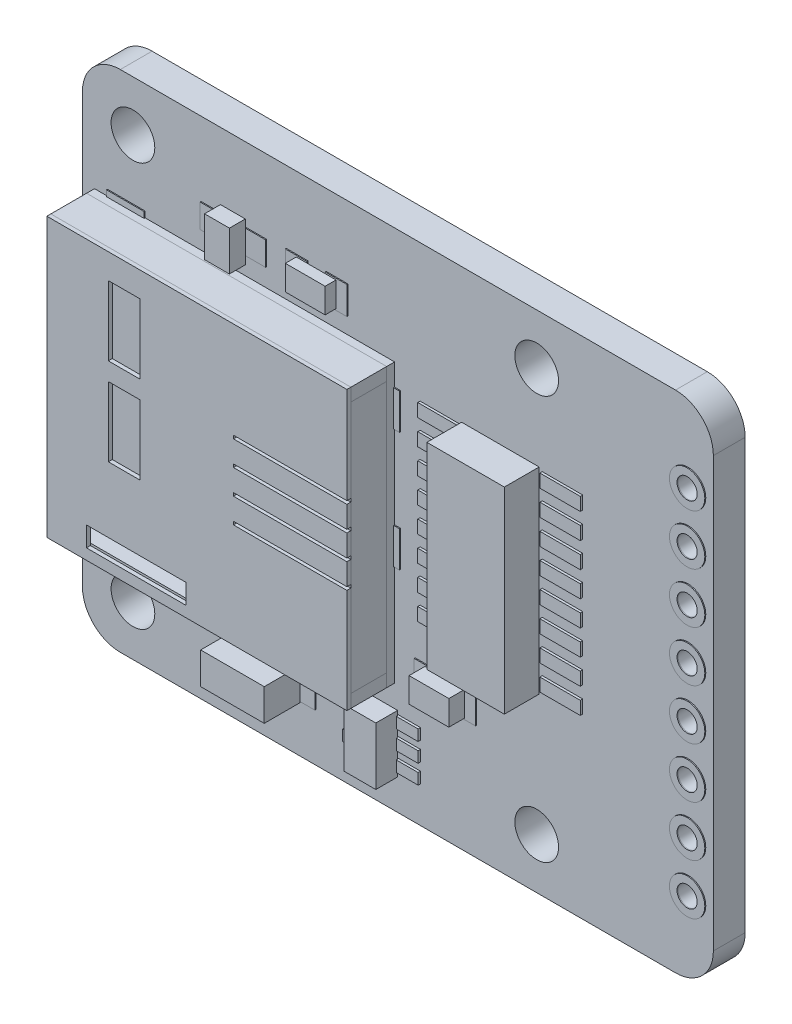
SolidWorks part; units mm, degrees
other "Capot_microSD"
other "PCB_Adafruit_ADA254"
ref_plane "Plan de face" through (0, 0, 0) normal (0, 0, 1) x (1, 0, 0)
ref_plane "Plan de dessus" through (0, 0, 0) normal (0, 1, 0) x (1, 0, 0)
ref_plane "Plan de droite" through (0, 0, 0) normal (1, 0, 0) x (0, 0, -1)
sketch "Esquisse1" plane through (0, 0, 0) normal (0, 0, 1) x (1, 0, 0)
  line L0 (29.845, 0) -> (1.905, 0)
  line L1 (0, 1.905) -> (0, 23.495)
  line L2 (1.905, 25.4) -> (29.845, 25.4)
  line L3 (31.75, 23.495) -> (31.75, 1.905)
  arc A0 (31.75, 1.905) -> (29.845, 0) centre (29.845, 1.905) cw
  arc A1 (1.905, 0) -> (0, 1.905) centre (1.905, 1.905) cw
  arc A2 (0, 23.495) -> (1.905, 25.4) centre (1.905, 23.495) cw
  arc A3 (29.845, 25.4) -> (31.75, 23.495) centre (29.845, 23.495) cw
  circle A4 centre (2.54, 22.86) radius 1.1
  circle A5 centre (2.54, 2.54) radius 1.1
  circle A6 centre (22.86, 22.86) radius 1.1
  circle A7 centre (22.86, 2.54) radius 1.1
  circle A8 centre (30.48, 3.683) radius 0.508
  circle A9 centre (30.48, 6.223) radius 0.508
  circle A10 centre (30.48, 8.763) radius 0.508
  circle A11 centre (30.48, 11.303) radius 0.508
  circle A12 centre (30.48, 13.843) radius 0.508
  circle A13 centre (30.48, 16.383) radius 0.508
  circle A14 centre (30.48, 18.923) radius 0.508
  circle A15 centre (30.48, 21.463) radius 0.508
extrude "PCB_Adafruit_Eagle_31_75x25_4_ep_ESTIMEE1_6" add sketch "Esquisse1" along normal blind 1.6 separate body
sketch "Esquisse2" plane through (0, 0, 0) normal (0, 0, 1) x (1, 0, 0)
  line L1 (0.608, 5.558) -> (15.708, 5.558)
  line L2 (0.608, 5.558) -> (0.608, 19.558)
  line L3 (0.608, 19.558) -> (15.708, 19.558)
  line L4 (15.708, 5.558) -> (15.708, 19.558)
extrude "MicroSD_base_H_ESTIMEE" add sketch "Esquisse2" along normal blind 0.4 from offset 1.6 separate body
sketch "Esquisse3" plane through (0, 0, 0) normal (0, 0, 1) x (1, 0, 0)
  line L1 (0.608, 5.558) -> (15.708, 5.558)
  line L2 (0.608, 5.558) -> (0.608, 6.208)
  line L3 (0.608, 6.208) -> (15.708, 6.208)
  line L4 (15.708, 5.558) -> (15.708, 6.208)
  line L6 (0.608, 18.908) -> (15.708, 18.908)
  line L7 (0.608, 18.908) -> (0.608, 19.558)
  line L8 (0.608, 19.558) -> (15.708, 19.558)
  line L9 (15.708, 18.908) -> (15.708, 19.558)
extrude "MicroSD_flancs" add sketch "Esquisse3" along normal blind 1.8 from offset 2 separate body
sketch "Esquisse4" plane through (0, 0, 0) normal (0, 0, 1) x (1, 0, 0)
  line L1 (15.058, 6.208) -> (15.708, 6.208)
  line L2 (15.058, 6.208) -> (15.058, 18.908)
  line L3 (15.058, 18.908) -> (15.708, 18.908)
  line L4 (15.708, 6.208) -> (15.708, 18.908)
extrude "MicroSD_fond" add sketch "Esquisse4" along normal blind 1.8 from offset 2 separate body
sketch "Esquisse5" plane through (0, 0, 0) normal (0, 0, 1) x (1, 0, 0)
  line L1 (0.608, 5.558) -> (15.708, 5.558)
  line L2 (0.608, 5.558) -> (0.608, 19.558)
  line L3 (0.608, 19.558) -> (15.708, 19.558)
  line L4 (15.708, 5.558) -> (15.708, 19.558)
extrude "MicroSD_capot_metallique" add sketch "Esquisse5" along normal blind 0.2 from offset 3.8 separate body
sketch "Esquisse6" plane through (0, 0, 0) normal (0, 0, 1) x (1, 0, 0)
  line L1 (3.7, 10.4) -> (5.3, 10.4)
  line L2 (3.7, 10.4) -> (3.7, 13.9)
  line L3 (3.7, 13.9) -> (5.3, 13.9)
  line L4 (5.3, 10.4) -> (5.3, 13.9)
  line L6 (3.7, 14.8) -> (5.3, 14.8)
  line L7 (3.7, 14.8) -> (3.7, 18.3)
  line L8 (3.7, 18.3) -> (5.3, 18.3)
  line L9 (5.3, 14.8) -> (5.3, 18.3)
  line L11 (2.6, 6.1) -> (7.6, 6.1)
  line L12 (2.6, 6.1) -> (2.6, 7.1)
  line L13 (2.6, 7.1) -> (7.6, 7.1)
  line L14 (7.6, 6.1) -> (7.6, 7.1)
extrude "Fenetres_capot_simplifiees" cut sketch "Esquisse6" against normal blind 0.2 from offset 4
sketch "Esquisse7" plane through (0, 0, 0) normal (0, 0, 1) x (1, 0, 0)
  line L1 (10, 10.8) -> (15.8, 10.8)
  line L2 (10, 10.8) -> (10, 10.96)
  line L3 (10, 10.96) -> (15.8, 10.96)
  line L4 (15.8, 10.8) -> (15.8, 10.96)
  line L6 (10, 12.05) -> (15.8, 12.05)
  line L7 (10, 12.05) -> (10, 12.21)
  line L8 (10, 12.21) -> (15.8, 12.21)
  line L9 (15.8, 12.05) -> (15.8, 12.21)
  line L11 (10, 13.3) -> (15.8, 13.3)
  line L12 (10, 13.3) -> (10, 13.46)
  line L13 (10, 13.46) -> (15.8, 13.46)
  line L14 (15.8, 13.3) -> (15.8, 13.46)
  line L16 (10, 14.55) -> (15.8, 14.55)
  line L17 (10, 14.55) -> (10, 14.71)
  line L18 (10, 14.71) -> (15.8, 14.71)
  line L19 (15.8, 14.55) -> (15.8, 14.71)
extrude "Fentes_capot_simplifiees" cut sketch "Esquisse7" against normal blind 0.2 from offset 4
sketch "Esquisse8" plane through (0, 0, 0) normal (0, 0, 1) x (1, 0, 0)
  line L1 (4.5, 10.208) -> (9.5, 10.208)
  line L2 (4.5, 10.208) -> (4.5, 10.558)
  line L3 (4.5, 10.558) -> (9.5, 10.558)
  line L4 (9.5, 10.208) -> (9.5, 10.558)
  line L6 (4.5, 11.308) -> (9.5, 11.308)
  line L7 (4.5, 11.308) -> (4.5, 11.658)
  line L8 (4.5, 11.658) -> (9.5, 11.658)
  line L9 (9.5, 11.308) -> (9.5, 11.658)
  line L11 (4.5, 12.408) -> (9.5, 12.408)
  line L12 (4.5, 12.408) -> (4.5, 12.758)
  line L13 (4.5, 12.758) -> (9.5, 12.758)
  line L14 (9.5, 12.408) -> (9.5, 12.758)
  line L16 (4.5, 13.508) -> (9.5, 13.508)
  line L17 (4.5, 13.508) -> (4.5, 13.858)
  line L18 (4.5, 13.858) -> (9.5, 13.858)
  line L19 (9.5, 13.508) -> (9.5, 13.858)
  line L21 (4.5, 14.608) -> (9.5, 14.608)
  line L22 (4.5, 14.608) -> (4.5, 14.958)
  line L23 (4.5, 14.958) -> (9.5, 14.958)
  line L24 (9.5, 14.608) -> (9.5, 14.958)
  line L26 (4.5, 15.708) -> (9.5, 15.708)
  line L27 (4.5, 15.708) -> (4.5, 16.058)
  line L28 (4.5, 16.058) -> (9.5, 16.058)
  line L29 (9.5, 15.708) -> (9.5, 16.058)
  line L31 (4.5, 16.808) -> (9.5, 16.808)
  line L32 (4.5, 16.808) -> (4.5, 17.158)
  line L33 (4.5, 17.158) -> (9.5, 17.158)
  line L34 (9.5, 16.808) -> (9.5, 17.158)
  line L36 (4.5, 17.908) -> (9.5, 17.908)
  line L37 (4.5, 17.908) -> (4.5, 18.258)
  line L38 (4.5, 18.258) -> (9.5, 18.258)
  line L39 (9.5, 17.908) -> (9.5, 18.258)
extrude "Contacts_microSD_simplifies" add sketch "Esquisse8" along normal blind 0.12 from offset 2 separate body
sketch "Esquisse9" plane through (0, 0, 0) normal (0, 0, 1) x (1, 0, 0)
  line L1 (19.132, 8.766) -> (23.032, 8.766)
  line L2 (19.132, 8.766) -> (19.132, 18.666)
  line L3 (19.132, 18.666) -> (23.032, 18.666)
  line L4 (23.032, 8.766) -> (23.032, 18.666)
extrude "IC1_position_Eagle" add sketch "Esquisse9" along normal blind 1.75 from offset 1.65 separate body
sketch "Esquisse10" plane through (0, 0, 0) normal (0, 0, 1) x (1, 0, 0)
  line L1 (14.313, 1.598) -> (15.913, 1.598)
  line L2 (14.313, 1.598) -> (14.313, 4.498)
  line L3 (14.313, 4.498) -> (15.913, 4.498)
  line L4 (15.913, 1.598) -> (15.913, 4.498)
extrude "IC2_position_Eagle" add sketch "Esquisse10" along normal blind 1.1 from offset 1.65 separate body
sketch "Esquisse11" plane through (0, 0, 0) normal (0, 0, 1) x (1, 0, 0)
  line L1 (7.798, 2.375) -> (10.998, 2.375)
  line L2 (7.798, 2.375) -> (7.798, 3.975)
  line L3 (7.798, 3.975) -> (10.998, 3.975)
  line L4 (10.998, 2.375) -> (10.998, 3.975)
extrude "C1_position_Eagle" add sketch "Esquisse11" along normal blind 1.8 from offset 1.65 separate body
sketch "Esquisse12" plane through (0, 0, 0) normal (0, 0, 1) x (1, 0, 0)
  line L1 (17.288, 5.852) -> (19.288, 5.852)
  line L2 (17.288, 5.852) -> (17.288, 7.102)
  line L3 (17.288, 7.102) -> (19.288, 7.102)
  line L4 (19.288, 5.852) -> (19.288, 7.102)
extrude "C2_position_Eagle" add sketch "Esquisse12" along normal blind 0.8 from offset 1.65 separate body
sketch "Esquisse13" plane through (0, 0, 0) normal (0, 0, 1) x (1, 0, 0)
  line L1 (6.995, 20.082) -> (8.245, 20.082)
  line L2 (6.995, 20.082) -> (6.995, 22.082)
  line L3 (6.995, 22.082) -> (8.245, 22.082)
  line L4 (8.245, 20.082) -> (8.245, 22.082)
extrude "ACT_position_Eagle" add sketch "Esquisse13" along normal blind 0.8 from offset 1.65 separate body
sketch "Esquisse14" plane through (0, 0, 0) normal (0, 0, 1) x (1, 0, 0)
  line L1 (10.811, 20.457) -> (12.811, 20.457)
  line L2 (10.811, 20.457) -> (10.811, 21.707)
  line L3 (10.811, 21.707) -> (12.811, 21.707)
  line L4 (12.811, 20.457) -> (12.811, 21.707)
extrude "R1_position_Eagle" add sketch "Esquisse14" along normal blind 0.55 from offset 1.65 separate body
sketch "Esquisse15" plane through (0, 0, 0) normal (0, 0, 1) x (1, 0, 0)
  line L1 (16.9926, 17.8308) -> (19.0246, 17.8308)
  line L2 (16.9926, 17.8308) -> (16.9926, 18.4912)
  line L3 (16.9926, 18.4912) -> (19.0246, 18.4912)
  line L4 (19.0246, 17.8308) -> (19.0246, 18.4912)
extrude "Pad_IC1_0" add sketch "Esquisse15" along normal blind 0.12 from offset 1.6 separate body
sketch "Esquisse16" plane through (0, 0, 0) normal (0, 0, 1) x (1, 0, 0)
  line L1 (23.1394, 17.8308) -> (25.1714, 17.8308)
  line L2 (23.1394, 17.8308) -> (23.1394, 18.4912)
  line L3 (23.1394, 18.4912) -> (25.1714, 18.4912)
  line L4 (25.1714, 17.8308) -> (25.1714, 18.4912)
extrude "Pad_IC1_1" add sketch "Esquisse16" along normal blind 0.12 from offset 1.6 separate body
sketch "Esquisse17" plane through (0, 0, 0) normal (0, 0, 1) x (1, 0, 0)
  line L1 (16.9926, 16.5608) -> (19.0246, 16.5608)
  line L2 (16.9926, 16.5608) -> (16.9926, 17.2212)
  line L3 (16.9926, 17.2212) -> (19.0246, 17.2212)
  line L4 (19.0246, 16.5608) -> (19.0246, 17.2212)
extrude "Pad_IC1_2" add sketch "Esquisse17" along normal blind 0.12 from offset 1.6 separate body
sketch "Esquisse18" plane through (0, 0, 0) normal (0, 0, 1) x (1, 0, 0)
  line L1 (16.9926, 15.2908) -> (19.0246, 15.2908)
  line L2 (16.9926, 15.2908) -> (16.9926, 15.9512)
  line L3 (16.9926, 15.9512) -> (19.0246, 15.9512)
  line L4 (19.0246, 15.2908) -> (19.0246, 15.9512)
extrude "Pad_IC1_3" add sketch "Esquisse18" along normal blind 0.12 from offset 1.6 separate body
sketch "Esquisse19" plane through (0, 0, 0) normal (0, 0, 1) x (1, 0, 0)
  line L1 (23.1394, 16.5608) -> (25.1714, 16.5608)
  line L2 (23.1394, 16.5608) -> (23.1394, 17.2212)
  line L3 (23.1394, 17.2212) -> (25.1714, 17.2212)
  line L4 (25.1714, 16.5608) -> (25.1714, 17.2212)
extrude "Pad_IC1_4" add sketch "Esquisse19" along normal blind 0.12 from offset 1.6 separate body
sketch "Esquisse20" plane through (0, 0, 0) normal (0, 0, 1) x (1, 0, 0)
  line L1 (23.1394, 15.2908) -> (25.1714, 15.2908)
  line L2 (23.1394, 15.2908) -> (23.1394, 15.9512)
  line L3 (23.1394, 15.9512) -> (25.1714, 15.9512)
  line L4 (25.1714, 15.2908) -> (25.1714, 15.9512)
extrude "Pad_IC1_5" add sketch "Esquisse20" along normal blind 0.12 from offset 1.6 separate body
sketch "Esquisse21" plane through (0, 0, 0) normal (0, 0, 1) x (1, 0, 0)
  line L1 (16.9926, 14.0208) -> (19.0246, 14.0208)
  line L2 (16.9926, 14.0208) -> (16.9926, 14.6812)
  line L3 (16.9926, 14.6812) -> (19.0246, 14.6812)
  line L4 (19.0246, 14.0208) -> (19.0246, 14.6812)
extrude "Pad_IC1_6" add sketch "Esquisse21" along normal blind 0.12 from offset 1.6 separate body
sketch "Esquisse22" plane through (0, 0, 0) normal (0, 0, 1) x (1, 0, 0)
  line L1 (23.1394, 14.0208) -> (25.1714, 14.0208)
  line L2 (23.1394, 14.0208) -> (23.1394, 14.6812)
  line L3 (23.1394, 14.6812) -> (25.1714, 14.6812)
  line L4 (25.1714, 14.0208) -> (25.1714, 14.6812)
extrude "Pad_IC1_7" add sketch "Esquisse22" along normal blind 0.12 from offset 1.6 separate body
sketch "Esquisse23" plane through (0, 0, 0) normal (0, 0, 1) x (1, 0, 0)
  line L1 (16.9926, 12.7508) -> (19.0246, 12.7508)
  line L2 (16.9926, 12.7508) -> (16.9926, 13.4112)
  line L3 (16.9926, 13.4112) -> (19.0246, 13.4112)
  line L4 (19.0246, 12.7508) -> (19.0246, 13.4112)
extrude "Pad_IC1_8" add sketch "Esquisse23" along normal blind 0.12 from offset 1.6 separate body
sketch "Esquisse24" plane through (0, 0, 0) normal (0, 0, 1) x (1, 0, 0)
  line L1 (23.1394, 12.7508) -> (25.1714, 12.7508)
  line L2 (23.1394, 12.7508) -> (23.1394, 13.4112)
  line L3 (23.1394, 13.4112) -> (25.1714, 13.4112)
  line L4 (25.1714, 12.7508) -> (25.1714, 13.4112)
extrude "Pad_IC1_9" add sketch "Esquisse24" along normal blind 0.12 from offset 1.6 separate body
sketch "Esquisse25" plane through (0, 0, 0) normal (0, 0, 1) x (1, 0, 0)
  line L1 (16.9926, 11.4808) -> (19.0246, 11.4808)
  line L2 (16.9926, 11.4808) -> (16.9926, 12.1412)
  line L3 (16.9926, 12.1412) -> (19.0246, 12.1412)
  line L4 (19.0246, 11.4808) -> (19.0246, 12.1412)
extrude "Pad_IC1_10" add sketch "Esquisse25" along normal blind 0.12 from offset 1.6 separate body
sketch "Esquisse26" plane through (0, 0, 0) normal (0, 0, 1) x (1, 0, 0)
  line L1 (16.9926, 10.2108) -> (19.0246, 10.2108)
  line L2 (16.9926, 10.2108) -> (16.9926, 10.8712)
  line L3 (16.9926, 10.8712) -> (19.0246, 10.8712)
  line L4 (19.0246, 10.2108) -> (19.0246, 10.8712)
extrude "Pad_IC1_11" add sketch "Esquisse26" along normal blind 0.12 from offset 1.6 separate body
sketch "Esquisse27" plane through (0, 0, 0) normal (0, 0, 1) x (1, 0, 0)
  line L1 (23.1394, 11.4808) -> (25.1714, 11.4808)
  line L2 (23.1394, 11.4808) -> (23.1394, 12.1412)
  line L3 (23.1394, 12.1412) -> (25.1714, 12.1412)
  line L4 (25.1714, 11.4808) -> (25.1714, 12.1412)
extrude "Pad_IC1_12" add sketch "Esquisse27" along normal blind 0.12 from offset 1.6 separate body
sketch "Esquisse28" plane through (0, 0, 0) normal (0, 0, 1) x (1, 0, 0)
  line L1 (23.1394, 10.2108) -> (25.1714, 10.2108)
  line L2 (23.1394, 10.2108) -> (23.1394, 10.8712)
  line L3 (23.1394, 10.8712) -> (25.1714, 10.8712)
  line L4 (25.1714, 10.2108) -> (25.1714, 10.8712)
extrude "Pad_IC1_13" add sketch "Esquisse28" along normal blind 0.12 from offset 1.6 separate body
sketch "Esquisse29" plane through (0, 0, 0) normal (0, 0, 1) x (1, 0, 0)
  line L1 (16.9926, 8.9408) -> (19.0246, 8.9408)
  line L2 (16.9926, 8.9408) -> (16.9926, 9.6012)
  line L3 (16.9926, 9.6012) -> (19.0246, 9.6012)
  line L4 (19.0246, 8.9408) -> (19.0246, 9.6012)
extrude "Pad_IC1_14" add sketch "Esquisse29" along normal blind 0.12 from offset 1.6 separate body
sketch "Esquisse30" plane through (0, 0, 0) normal (0, 0, 1) x (1, 0, 0)
  line L1 (23.1394, 8.9408) -> (25.1714, 8.9408)
  line L2 (23.1394, 8.9408) -> (23.1394, 9.6012)
  line L3 (23.1394, 9.6012) -> (25.1714, 9.6012)
  line L4 (25.1714, 8.9408) -> (25.1714, 9.6012)
extrude "Pad_IC1_15" add sketch "Esquisse30" along normal blind 0.12 from offset 1.6 separate body
sketch "Esquisse31" plane through (0, 0, 0) normal (0, 0, 1) x (1, 0, 0)
  line L1 (1.258, 18.458) -> (3.158, 18.458)
  line L2 (1.258, 18.458) -> (1.258, 19.858)
  line L3 (1.258, 19.858) -> (3.158, 19.858)
  line L4 (3.158, 18.458) -> (3.158, 19.858)
extrude "Pad_X1_0" add sketch "Esquisse31" along normal blind 0.05 from offset 1.6 separate body
sketch "Esquisse32" plane through (0, 0, 0) normal (0, 0, 1) x (1, 0, 0)
  line L1 (0.358, 5.258) -> (2.258, 5.258)
  line L2 (0.358, 5.258) -> (0.358, 6.658)
  line L3 (0.358, 6.658) -> (2.258, 6.658)
  line L4 (2.258, 5.258) -> (2.258, 6.658)
extrude "Pad_X1_1" add sketch "Esquisse32" along normal blind 0.05 from offset 1.6 separate body
sketch "Esquisse33" plane through (0, 0, 0) normal (0, 0, 1) x (1, 0, 0)
  line L1 (14.608, 16.658) -> (16.008, 16.658)
  line L2 (14.608, 16.658) -> (14.608, 18.458)
  line L3 (14.608, 18.458) -> (16.008, 18.458)
  line L4 (16.008, 16.658) -> (16.008, 18.458)
extrude "Pad_X1_2" add sketch "Esquisse33" along normal blind 0.05 from offset 1.6 separate body
sketch "Esquisse34" plane through (0, 0, 0) normal (0, 0, 1) x (1, 0, 0)
  line L1 (14.608, 10.658) -> (16.008, 10.658)
  line L2 (14.608, 10.658) -> (14.608, 12.458)
  line L3 (14.608, 12.458) -> (16.008, 12.458)
  line L4 (16.008, 10.658) -> (16.008, 12.458)
extrude "Pad_X1_3" add sketch "Esquisse34" along normal blind 0.05 from offset 1.6 separate body
sketch "Esquisse35" plane through (0, 0, 0) normal (0, 0, 1) x (1, 0, 0)
  line L1 (4.358, 17.908) -> (5.858, 17.908)
  line L2 (4.358, 17.908) -> (4.358, 18.608)
  line L3 (4.358, 18.608) -> (5.858, 18.608)
  line L4 (5.858, 17.908) -> (5.858, 18.608)
extrude "Pad_X1_4" add sketch "Esquisse35" along normal blind 0.05 from offset 1.6 separate body
sketch "Esquisse36" plane through (0, 0, 0) normal (0, 0, 1) x (1, 0, 0)
  line L1 (4.358, 16.808) -> (5.858, 16.808)
  line L2 (4.358, 16.808) -> (4.358, 17.508)
  line L3 (4.358, 17.508) -> (5.858, 17.508)
  line L4 (5.858, 16.808) -> (5.858, 17.508)
extrude "Pad_X1_5" add sketch "Esquisse36" along normal blind 0.05 from offset 1.6 separate body
sketch "Esquisse37" plane through (0, 0, 0) normal (0, 0, 1) x (1, 0, 0)
  line L1 (3.958, 15.708) -> (5.458, 15.708)
  line L2 (3.958, 15.708) -> (3.958, 16.408)
  line L3 (3.958, 16.408) -> (5.458, 16.408)
  line L4 (5.458, 15.708) -> (5.458, 16.408)
extrude "Pad_X1_6" add sketch "Esquisse37" along normal blind 0.05 from offset 1.6 separate body
sketch "Esquisse38" plane through (0, 0, 0) normal (0, 0, 1) x (1, 0, 0)
  line L1 (4.358, 14.608) -> (5.858, 14.608)
  line L2 (4.358, 14.608) -> (4.358, 15.308)
  line L3 (4.358, 15.308) -> (5.858, 15.308)
  line L4 (5.858, 14.608) -> (5.858, 15.308)
extrude "Pad_X1_7" add sketch "Esquisse38" along normal blind 0.05 from offset 1.6 separate body
sketch "Esquisse39" plane through (0, 0, 0) normal (0, 0, 1) x (1, 0, 0)
  line L1 (3.958, 13.508) -> (5.458, 13.508)
  line L2 (3.958, 13.508) -> (3.958, 14.208)
  line L3 (3.958, 14.208) -> (5.458, 14.208)
  line L4 (5.458, 13.508) -> (5.458, 14.208)
extrude "Pad_X1_8" add sketch "Esquisse39" along normal blind 0.05 from offset 1.6 separate body
sketch "Esquisse40" plane through (0, 0, 0) normal (0, 0, 1) x (1, 0, 0)
  line L1 (4.358, 12.408) -> (5.858, 12.408)
  line L2 (4.358, 12.408) -> (4.358, 13.108)
  line L3 (4.358, 13.108) -> (5.858, 13.108)
  line L4 (5.858, 12.408) -> (5.858, 13.108)
extrude "Pad_X1_9" add sketch "Esquisse40" along normal blind 0.05 from offset 1.6 separate body
sketch "Esquisse41" plane through (0, 0, 0) normal (0, 0, 1) x (1, 0, 0)
  line L1 (4.758, 11.308) -> (6.258, 11.308)
  line L2 (4.758, 11.308) -> (4.758, 12.008)
  line L3 (4.758, 12.008) -> (6.258, 12.008)
  line L4 (6.258, 11.308) -> (6.258, 12.008)
extrude "Pad_X1_10" add sketch "Esquisse41" along normal blind 0.05 from offset 1.6 separate body
sketch "Esquisse42" plane through (0, 0, 0) normal (0, 0, 1) x (1, 0, 0)
  line L1 (4.358, 10.208) -> (5.858, 10.208)
  line L2 (4.358, 10.208) -> (4.358, 10.908)
  line L3 (4.358, 10.908) -> (5.858, 10.908)
  line L4 (5.858, 10.208) -> (5.858, 10.908)
extrude "Pad_X1_11" add sketch "Esquisse42" along normal blind 0.05 from offset 1.6 separate body
sketch "Esquisse43" plane through (0, 0, 0) normal (0, 0, 1) x (1, 0, 0)
  line L1 (15.813, 1.823) -> (17.013, 1.823)
  line L2 (15.813, 1.823) -> (15.813, 2.373)
  line L3 (15.813, 2.373) -> (17.013, 2.373)
  line L4 (17.013, 1.823) -> (17.013, 2.373)
extrude "Pad_IC2_0" add sketch "Esquisse43" along normal blind 0.12 from offset 1.6 separate body
sketch "Esquisse44" plane through (0, 0, 0) normal (0, 0, 1) x (1, 0, 0)
  line L1 (15.813, 2.773) -> (17.013, 2.773)
  line L2 (15.813, 2.773) -> (15.813, 3.323)
  line L3 (15.813, 3.323) -> (17.013, 3.323)
  line L4 (17.013, 2.773) -> (17.013, 3.323)
extrude "Pad_IC2_1" add sketch "Esquisse44" along normal blind 0.12 from offset 1.6 separate body
sketch "Esquisse45" plane through (0, 0, 0) normal (0, 0, 1) x (1, 0, 0)
  line L1 (15.813, 3.723) -> (17.013, 3.723)
  line L2 (15.813, 3.723) -> (15.813, 4.273)
  line L3 (15.813, 4.273) -> (17.013, 4.273)
  line L4 (17.013, 3.723) -> (17.013, 4.273)
extrude "Pad_IC2_2" add sketch "Esquisse45" along normal blind 0.12 from offset 1.6 separate body
sketch "Esquisse46" plane through (0, 0, 0) normal (0, 0, 1) x (1, 0, 0)
  line L1 (13.213, 3.723) -> (14.413, 3.723)
  line L2 (13.213, 3.723) -> (13.213, 4.273)
  line L3 (13.213, 4.273) -> (14.413, 4.273)
  line L4 (14.413, 3.723) -> (14.413, 4.273)
extrude "Pad_IC2_3" add sketch "Esquisse46" along normal blind 0.12 from offset 1.6 separate body
sketch "Esquisse47" plane through (0, 0, 0) normal (0, 0, 1) x (1, 0, 0)
  line L1 (13.213, 1.823) -> (14.413, 1.823)
  line L2 (13.213, 1.823) -> (13.213, 2.373)
  line L3 (13.213, 2.373) -> (14.413, 2.373)
  line L4 (14.413, 1.823) -> (14.413, 2.373)
extrude "Pad_IC2_4" add sketch "Esquisse47" along normal blind 0.12 from offset 1.6 separate body
sketch "Esquisse48" plane through (0, 0, 0) normal (0, 0, 1) x (1, 0, 0)
  line L1 (9.798, 2.425) -> (11.748, 2.425)
  line L2 (9.798, 2.425) -> (9.798, 3.925)
  line L3 (9.798, 3.925) -> (11.748, 3.925)
  line L4 (11.748, 2.425) -> (11.748, 3.925)
extrude "Pad_C1_0" add sketch "Esquisse48" along normal blind 0.05 from offset 1.6 separate body
sketch "Esquisse49" plane through (0, 0, 0) normal (0, 0, 1) x (1, 0, 0)
  line L1 (7.048, 2.425) -> (8.998, 2.425)
  line L2 (7.048, 2.425) -> (7.048, 3.925)
  line L3 (7.048, 3.925) -> (8.998, 3.925)
  line L4 (8.998, 2.425) -> (8.998, 3.925)
extrude "Pad_C1_1" add sketch "Esquisse49" along normal blind 0.05 from offset 1.6 separate body
sketch "Esquisse50" plane through (0, 0, 0) normal (0, 0, 1) x (1, 0, 0)
  line L1 (16.738, 5.777) -> (17.838, 5.777)
  line L2 (16.738, 5.777) -> (16.738, 7.177)
  line L3 (16.738, 7.177) -> (17.838, 7.177)
  line L4 (17.838, 5.777) -> (17.838, 7.177)
extrude "Pad_C2_0" add sketch "Esquisse50" along normal blind 0.05 from offset 1.6 separate body
sketch "Esquisse51" plane through (0, 0, 0) normal (0, 0, 1) x (1, 0, 0)
  line L1 (18.738, 5.777) -> (19.838, 5.777)
  line L2 (18.738, 5.777) -> (18.738, 7.177)
  line L3 (18.738, 7.177) -> (19.838, 7.177)
  line L4 (19.838, 5.777) -> (19.838, 7.177)
extrude "Pad_C2_1" add sketch "Esquisse51" along normal blind 0.05 from offset 1.6 separate body
sketch "Esquisse52" plane through (0, 0, 0) normal (0, 0, 1) x (1, 0, 0)
  circle A0 centre (30.48, 3.683) radius 0.889
  circle A1 centre (30.48, 3.683) radius 0.508
extrude "Anneau_JP1_0" add sketch "Esquisse52" along normal blind 0.05 from offset 1.6 separate body
sketch "Esquisse53" plane through (0, 0, 0) normal (0, 0, 1) x (1, 0, 0)
  circle A0 centre (30.48, 6.223) radius 0.889
  circle A1 centre (30.48, 6.223) radius 0.508
extrude "Anneau_JP1_1" add sketch "Esquisse53" along normal blind 0.05 from offset 1.6 separate body
sketch "Esquisse54" plane through (0, 0, 0) normal (0, 0, 1) x (1, 0, 0)
  circle A0 centre (30.48, 8.763) radius 0.889
  circle A1 centre (30.48, 8.763) radius 0.508
extrude "Anneau_JP1_2" add sketch "Esquisse54" along normal blind 0.05 from offset 1.6 separate body
sketch "Esquisse55" plane through (0, 0, 0) normal (0, 0, 1) x (1, 0, 0)
  circle A0 centre (30.48, 11.303) radius 0.889
  circle A1 centre (30.48, 11.303) radius 0.508
extrude "Anneau_JP1_3" add sketch "Esquisse55" along normal blind 0.05 from offset 1.6 separate body
sketch "Esquisse56" plane through (0, 0, 0) normal (0, 0, 1) x (1, 0, 0)
  circle A0 centre (30.48, 13.843) radius 0.889
  circle A1 centre (30.48, 13.843) radius 0.508
extrude "Anneau_JP1_4" add sketch "Esquisse56" along normal blind 0.05 from offset 1.6 separate body
sketch "Esquisse57" plane through (0, 0, 0) normal (0, 0, 1) x (1, 0, 0)
  circle A0 centre (30.48, 16.383) radius 0.889
  circle A1 centre (30.48, 16.383) radius 0.508
extrude "Anneau_JP1_5" add sketch "Esquisse57" along normal blind 0.05 from offset 1.6 separate body
sketch "Esquisse58" plane through (0, 0, 0) normal (0, 0, 1) x (1, 0, 0)
  circle A0 centre (30.48, 18.923) radius 0.889
  circle A1 centre (30.48, 18.923) radius 0.508
extrude "Anneau_JP1_6" add sketch "Esquisse58" along normal blind 0.05 from offset 1.6 separate body
sketch "Esquisse59" plane through (0, 0, 0) normal (0, 0, 1) x (1, 0, 0)
  circle A0 centre (30.48, 21.463) radius 0.889
  circle A1 centre (30.48, 21.463) radius 0.508
extrude "Anneau_JP1_7" add sketch "Esquisse59" along normal blind 0.05 from offset 1.6 separate body
sketch "Esquisse60" plane through (0, 0, 0) normal (0, 0, 1) x (1, 0, 0)
  line L1 (8.07, 20.482) -> (9.27, 20.482)
  line L2 (8.07, 20.482) -> (8.07, 21.682)
  line L3 (8.07, 21.682) -> (9.27, 21.682)
  line L4 (9.27, 20.482) -> (9.27, 21.682)
extrude "Pad_ACT_0" add sketch "Esquisse60" along normal blind 0.05 from offset 1.6 separate body
sketch "Esquisse61" plane through (0, 0, 0) normal (0, 0, 1) x (1, 0, 0)
  line L1 (5.97, 20.482) -> (7.17, 20.482)
  line L2 (5.97, 20.482) -> (5.97, 21.682)
  line L3 (5.97, 21.682) -> (7.17, 21.682)
  line L4 (7.17, 20.482) -> (7.17, 21.682)
extrude "Pad_ACT_1" add sketch "Esquisse61" along normal blind 0.05 from offset 1.6 separate body
sketch "Esquisse62" plane through (0, 0, 0) normal (0, 0, 1) x (1, 0, 0)
  line L1 (12.261, 20.382) -> (13.361, 20.382)
  line L2 (12.261, 20.382) -> (12.261, 21.782)
  line L3 (12.261, 21.782) -> (13.361, 21.782)
  line L4 (13.361, 20.382) -> (13.361, 21.782)
extrude "Pad_R1_0" add sketch "Esquisse62" along normal blind 0.05 from offset 1.6 separate body
sketch "Esquisse63" plane through (0, 0, 0) normal (0, 0, 1) x (1, 0, 0)
  line L1 (10.261, 20.382) -> (11.361, 20.382)
  line L2 (10.261, 20.382) -> (10.261, 21.782)
  line L3 (10.261, 21.782) -> (11.361, 21.782)
  line L4 (11.361, 20.382) -> (11.361, 21.782)
extrude "Pad_R1_1" add sketch "Esquisse63" along normal blind 0.05 from offset 1.6 separate body
